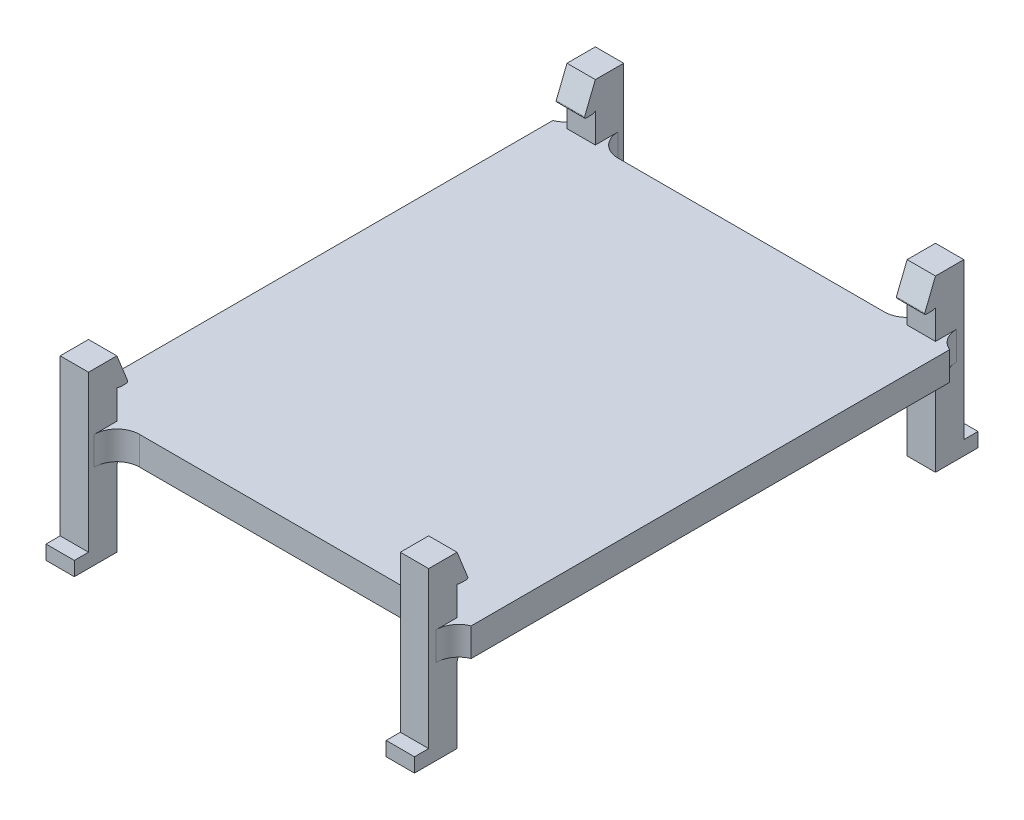
SolidWorks part; units mm, degrees
material "PLA"
ref_plane "Front Plane" through (0, 0, 0) normal (0, 0, 1) x (1, 0, 0)
ref_plane "Top Plane" through (0, 0, 0) normal (0, 1, 0) x (1, 0, 0)
ref_plane "Right Plane" through (0, 0, 0) normal (1, 0, 0) x (0, 0, -1)
sketch "Sketch1" plane through (0, 0, 0) normal (0, 1, 0) x (1, 0, 0)
  line L1 (-2.0818, -16.1144) -> (42.3682, -16.1144)
  line L2 (-2.0818, -16.1144) -> (-2.0818, 37.4796)
  line L3 (-2.0818, 37.4796) -> (42.3682, 37.4796)
  line L4 (42.3682, -16.1144) -> (42.3682, 37.4796)
  dimension "D1" = 53.594
  dimension "D2" = 44.45
extrude "Boss-Extrude1" add sketch "Sketch1" along normal blind 3.175
sketch "Sketch2" plane through (0, 0, 16.1144) normal (0, 0, 1) x (1, 0, 0)
  line L0 (-2.0818, 3.175) -> (42.3682, 3.175) construction
  line L1 (-0.4943, 9.525) -> (2.6807, 9.525)
  line L2 (-0.4943, 9.525) -> (-0.4943, -9.525)
  line L3 (-0.4943, -9.525) -> (2.6807, -9.525)
  line L4 (2.6807, 9.525) -> (2.6807, -9.525)
  line L5 (-2.0818, 3.175) -> (-2.0818, 0) construction
  line L6 (20.1432, 10.6693) -> (20.1432, -12.7496) construction
  line L7 (40.7807, -9.525) -> (37.6057, -9.525)
  line L8 (37.6057, 9.525) -> (37.6057, -9.525)
  line L9 (40.7807, 9.525) -> (37.6057, 9.525)
  line L10 (40.7807, 9.525) -> (40.7807, -9.525)
  dimension "D1" = 3.175
  dimension "D2" = 19.05
  dimension "D3" = 6.35
  dimension "D4" = 1.5875
extrude "Boss-Extrude2" add sketch "Sketch2" along normal blind 3.175
sketch "Sketch4" plane through (0, 0, -37.4796) normal (0, 0, -1) x (-1, 0, 0)
  line L0 (0.4943, 0) -> (0.4943, -9.525) construction
  line L1 (-2.6807, 9.525) -> (0.4943, 9.525)
  line L2 (-2.6807, 9.525) -> (-2.6807, -9.525)
  line L3 (-2.6807, -9.525) -> (0.4943, -9.525)
  line L4 (0.4943, 9.525) -> (0.4943, -9.525)
  line L6 (-40.7807, 9.525) -> (-37.6057, 9.525)
  line L7 (-40.7807, 9.525) -> (-40.7807, -9.525)
  line L8 (-40.7807, -9.525) -> (-37.6057, -9.525)
  line L9 (-37.6057, 9.525) -> (-37.6057, -9.525)
extrude "Boss-Extrude3" add sketch "Sketch4" along normal blind 3.175
sketch "Sketch9" plane through (40.7807, 0, 0) normal (1, 0, 0) x (0, 0, -1)
  line L0 (-16.1144, 9.525) -> (-14.8444, 6.35)
  line L1 (-14.8444, 6.35) -> (-15.981, 6.2599) construction
  line L2 (-16.1144, 3.175) -> (-16.1144, 9.525) construction
  line L3 (-15.981, 6.2599) -> (-16.1144, 6.477) construction
  line L4 (-16.1144, 9.525) -> (-16.1144, 6.477)
  line L5 (-16.1144, 3.175) -> (37.4796, 3.175) construction
  line L6 (10.6826, 13.3716) -> (10.6826, -13.8849) construction
  line L7 (37.4796, 9.525) -> (36.2096, 6.35)
  line L8 (36.2096, 6.35) -> (37.3462, 6.2599) construction
  line L9 (37.3462, 6.2599) -> (37.4796, 6.477) construction
  line L10 (37.4796, 9.525) -> (37.4796, 6.477)
  spline S0 degree 2 poles (-14.8444, 6.35) (-15.981, 6.2599) (-16.1144, 6.477) knots 0 0 0 1 1 1
  spline S1 degree 2 poles (36.2096, 6.35) (37.3462, 6.2599) (37.4796, 6.477) knots 0 0 0 1 1 1
  dimension "D1" = 3.302
  dimension "D2" = 1.27
extrude "Boss-Extrude4" add sketch "Sketch9" against normal blind 3.175
sketch "Sketch10" plane through (-0.4943, 0, 0) normal (-1, 0, 0) x (0, 0, 1)
  line L0 (-37.4796, 9.525) -> (-36.2096, 6.35)
  line L1 (-36.2096, 6.35) -> (-37.2535, 6.2219) construction
  line L2 (-37.2535, 6.2219) -> (-37.4796, 6.477) construction
  line L4 (-37.4796, 9.525) -> (-37.4796, 6.477)
  line L5 (-37.4796, 3.175) -> (-37.4796, 9.525) construction
  line L7 (-10.6826, 13.0166) -> (-10.6826, -14.6222) construction
  line L8 (16.1144, 9.525) -> (14.8444, 6.35)
  line L9 (14.8444, 6.35) -> (15.8883, 6.2219) construction
  line L10 (15.8883, 6.2219) -> (16.1144, 6.477) construction
  line L11 (16.1144, 9.525) -> (16.1144, 6.477)
  spline S0 degree 2 poles (-36.2096, 6.35) (-37.2535, 6.2219) (-37.4796, 6.477) knots 0 0 0 1 1 1
  spline S1 degree 2 poles (14.8444, 6.35) (15.8883, 6.2219) (16.1144, 6.477) knots 0 0 0 1 1 1
  dimension "D1" = 1.27
extrude "Boss-Extrude5" add sketch "Sketch10" against normal blind 3.175
sketch "Sketch11" plane through (0, 0, 19.2894) normal (0, 0, 1) x (1, 0, 0)
  line L0 (2.6807, -9.525) -> (2.6807, 9.525) construction
  line L1 (-0.4943, -9.525) -> (2.6807, -9.525)
  line L2 (-0.4943, -9.525) -> (-0.4943, -7.9375)
  line L3 (-0.4943, -7.9375) -> (2.6807, -7.9375)
  line L4 (2.6807, -9.525) -> (2.6807, -7.9375)
  line L5 (20.1432, 3.175) -> (20.1432, -12.2426) construction
  line L6 (2.6807, 3.175) -> (37.6057, 3.175) construction
  line L7 (40.7807, -7.9375) -> (37.6057, -7.9375)
  line L8 (37.6057, -9.525) -> (37.6057, -7.9375)
  line L9 (40.7807, -9.525) -> (37.6057, -9.525)
  line L10 (40.7807, -9.525) -> (40.7807, -7.9375)
  dimension "D1" = 1.5875
extrude "Boss-Extrude6" add sketch "Sketch11" along normal blind 1.5875
sketch "Sketch12" plane through (0, 0, -40.6546) normal (0, 0, -1) x (-1, 0, 0)
  line L0 (-37.6057, -9.525) -> (-37.6057, 9.525) construction
  line L1 (-40.7807, -9.525) -> (-37.6057, -9.525)
  line L2 (-40.7807, -9.525) -> (-40.7807, -7.9375)
  line L3 (-40.7807, -7.9375) -> (-37.6057, -7.9375)
  line L4 (-37.6057, -9.525) -> (-37.6057, -7.9375)
  line L5 (-20.1432, 0) -> (-20.1432, -11.4799) construction
  line L6 (-37.6057, 0) -> (-2.6807, 0) construction
  line L7 (0.4943, -7.9375) -> (-2.6807, -7.9375)
  line L8 (-2.6807, -9.525) -> (-2.6807, -7.9375)
  line L9 (0.4943, -9.525) -> (-2.6807, -9.525)
  line L10 (0.4943, -9.525) -> (0.4943, -7.9375)
  dimension "D1" = 1.5875
extrude "Boss-Extrude7" add sketch "Sketch12" along normal blind 1.5875
fillet "Fillet1" radius 2.54 8 edges at (37.6057, 1.5875, -37.4796) (-0.4943, 1.5875, -37.4796) (2.6807, 1.5875, -37.4796) (40.7807, 1.5875, -37.4796) (2.6807, 1.5875, 16.1144) (-0.4943, 1.5875, 16.1144) (37.6057, 1.5875, 16.1144) (40.7807, 1.5875, 16.1144)
fillet "Fillet2" radius 0.127 4 edges at (39.1932, 6.35, 14.8444) (39.1932, 6.35, -36.2096) (1.0932, 6.35, -36.2096) (1.0932, 6.35, 14.8444)
fillet "Fillet3" radius 1.27 4 edges at (39.1932, 0, 16.1144) (1.0932, 0, 16.1144) (39.1932, 0, -37.4796) (1.0932, 0, -37.4796)
